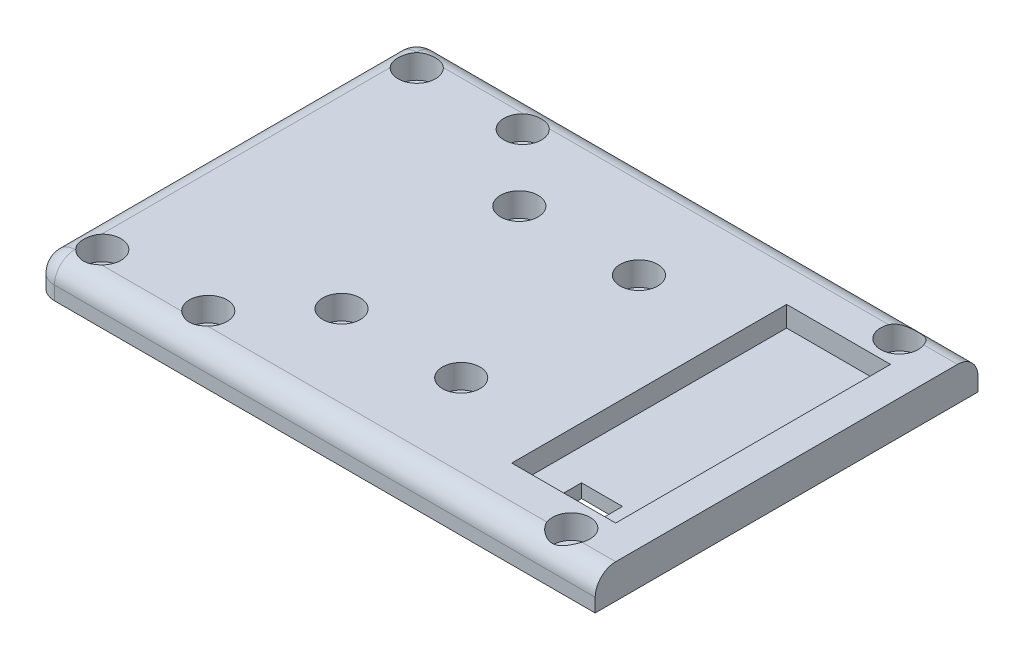
SolidWorks part; units mm, degrees
ref_plane "Front Plane" through (0, 0, 0) normal (0, 0, 1) x (1, 0, 0)
ref_plane "Top Plane" through (0, 0, 0) normal (0, 1, 0) x (1, 0, 0)
ref_plane "Right Plane" through (0, 0, 0) normal (1, 0, 0) x (0, 0, -1)
sketch "Sketch1" plane through (0, 0, 0) normal (0, 1, 0) x (1, 0, 0)
  line L1 (-41.05, -28) -> (41.05, -28)
  line L2 (-41.05, -28) -> (-41.05, 28)
  line L3 (-41.05, 28) -> (41.05, 28)
  line L4 (41.05, -28) -> (41.05, 28)
  line L5 (-41.05, -28) -> (41.05, 28) construction
  line L6 (-41.05, 28) -> (41.05, -28) construction
  point P0 (0, 0)
  dimension "D1" = 82.1
  dimension "D2" = 56
extrude "Boss-Extrude1" add sketch "Sketch1" along normal blind 5
hole_wizard "CBORE for M2.5 SHCS1" positions "Sketch2" profile "Sketch3" counterbore size "M2.5" standard "ANSI Metric" end condition through all
sketch "Sketch2" plane through (0, 5, 0) normal (0, 1, 0) x (1, 0, 0)
  line L0 (-41.05, 28) -> (-41.05, -28) construction
  line L1 (41.05, 28) -> (-41.05, 28) construction
  line L2 (-41.05, -28) -> (41.05, -28) construction
  point P0 (-36.05, 23)
  point P2 (-36.05, -23)
  point P4 (-20.55, -23)
  point P6 (-20.55, 23)
  point P20 (-11.05, -13)
  point P22 (-11.05, 13)
  point P27 (6.45, 13)
  point P29 (6.45, -13)
  point P35 (33.55, 24)
  point P37 (33.55, -24)
  dimension "D1" = 5
  dimension "D2" = 20.5
  dimension "D3" = 5
  dimension "D4" = 5
  dimension "D5" = 15
  dimension "D6" = 15
  dimension "D7" = 30
  dimension "D8" = 47.5
  dimension "D9" = 4
  dimension "D10" = 4
  dimension "D11" = 74.6
sketch "Sketch3" plane through (-36.05, 5, -23) normal (1, 0, 0) x (0, 0, 1)
  line L0 (0, 0) -> (0, 5)
  line L1 (0, 5) -> (1.45, 5)
  line L3 (1.45, 5) -> (1.45, 3.5)
  line L4 (1.45, 3.5) -> (2.75, 3.5)
  line L5 (2.75, 3.5) -> (2.75, 0)
  line L7 (2.75, 0) -> (0, 0)
  line L11 (0, -6.35) -> (0, 107.95) construction
  dimension "Thru Hole Dia." = 2.9
  dimension "Thru Hole Depth" = 5
  dimension "C'Bore Dia." = 5.5
  dimension "C'Bore Depth" = 3.5
fillet "Fillet1" radius 3 2 edges at (-41.05, 2.5, -28) (-41.05, 2.5, 28)
fillet "Fillet2" radius 3 5 edges at (1.5, 5, -28) (-40.1713, 5, -27.1213) (1.5, 5, 28) (-40.1713, 5, 27.1213) (-41.05, 5, 0)
sketch "Sketch4" plane through (0, 5, 0) normal (0, 1, 0) x (1, 0, 0)
  line L0 (41.05, 0) -> (-38.05, 0)
  line L1 (21.05, 20) -> (36.05, 20)
  line L2 (21.05, 20) -> (21.05, -20)
  line L3 (21.05, -20) -> (36.05, -20)
  line L4 (36.05, 20) -> (36.05, -20)
  line L5 (21.05, 20) -> (36.05, -20) construction
  line L6 (21.05, -20) -> (36.05, 20) construction
  line L7 (41.05, -25) -> (41.05, 25) construction
  line L8 (-38.05, 21.1125) -> (-38.05, -21.1125) construction
  point P0 (28.55, 0)
  dimension "D1" = 15
  dimension "D2" = 40
  dimension "D3" = 5
extrude "Cut-Extrude1" cut sketch "Sketch4" against normal blind 3 contours L2 L3 L4 L1
sketch "Sketch5" plane through (0, 2, 0) normal (0, 1, 0) x (1, 0, 0)
  line L0 (28.55, -20) -> (28.55, 20) construction
  line L1 (31.55, -17.5) -> (25.55, -17.5)
  line L2 (31.55, -17.5) -> (31.55, -14.5)
  line L3 (31.55, -14.5) -> (25.55, -14.5)
  line L4 (25.55, -17.5) -> (25.55, -14.5)
  line L5 (31.55, -17.5) -> (25.55, -14.5) construction
  line L6 (31.55, -14.5) -> (25.55, -17.5) construction
  line L7 (21.05, -20) -> (36.05, -20) construction
  line L8 (21.05, 20) -> (36.05, 20) construction
  line L9 (21.05, -20) -> (36.05, -20) construction
  point P0 (28.55, -16)
  dimension "D1" = 3
  dimension "D2" = 6
  dimension "D3" = 4
extrude "Cut-Extrude2" cut sketch "Sketch5" against normal through all
other "Move Face1" flip direction yes face at (28.55, 3.5, 20) face at (36.05, 3.5, 0) face at (28.55, 3.5, -20) face at (21.05, 3.5, 0) offset 0.1 parameters "D1"=0.1
